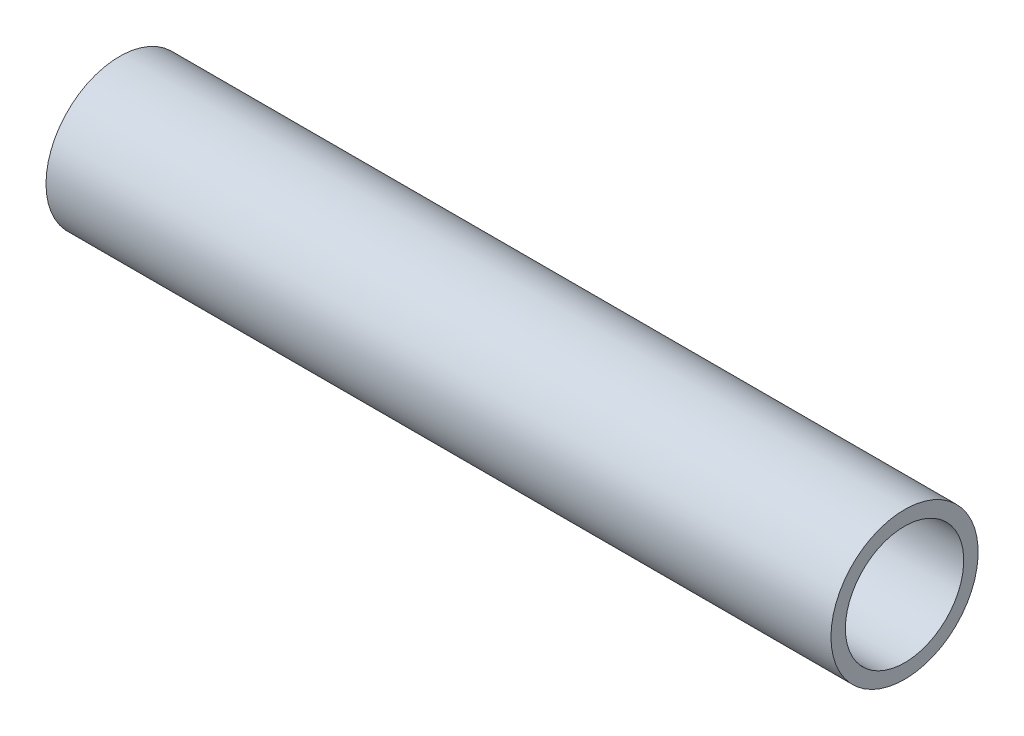
SolidWorks part; units mm, degrees
material "7075-T6 (SN)"
ref_plane "Front Plane" through (0, 0, 0) normal (0, 0, 1) x (1, 0, 0)
ref_plane "Top Plane" through (0, 0, 0) normal (0, 1, 0) x (1, 0, 0)
ref_plane "Right Plane" through (0, 0, 0) normal (1, 0, 0) x (0, 0, -1)
sketch "Sketch1" plane through (0, 0, 0) normal (1, 0, 0) x (0, 0, -1)
  circle A0 centre (0, 0) radius 45.9486
  circle A1 centre (0, 0) radius 57.15
  dimension "D1" = 91.8972
  dimension "D2" = 114.3
extrude "Boss-Extrude1" add sketch "Sketch1" along normal blind 609.6
